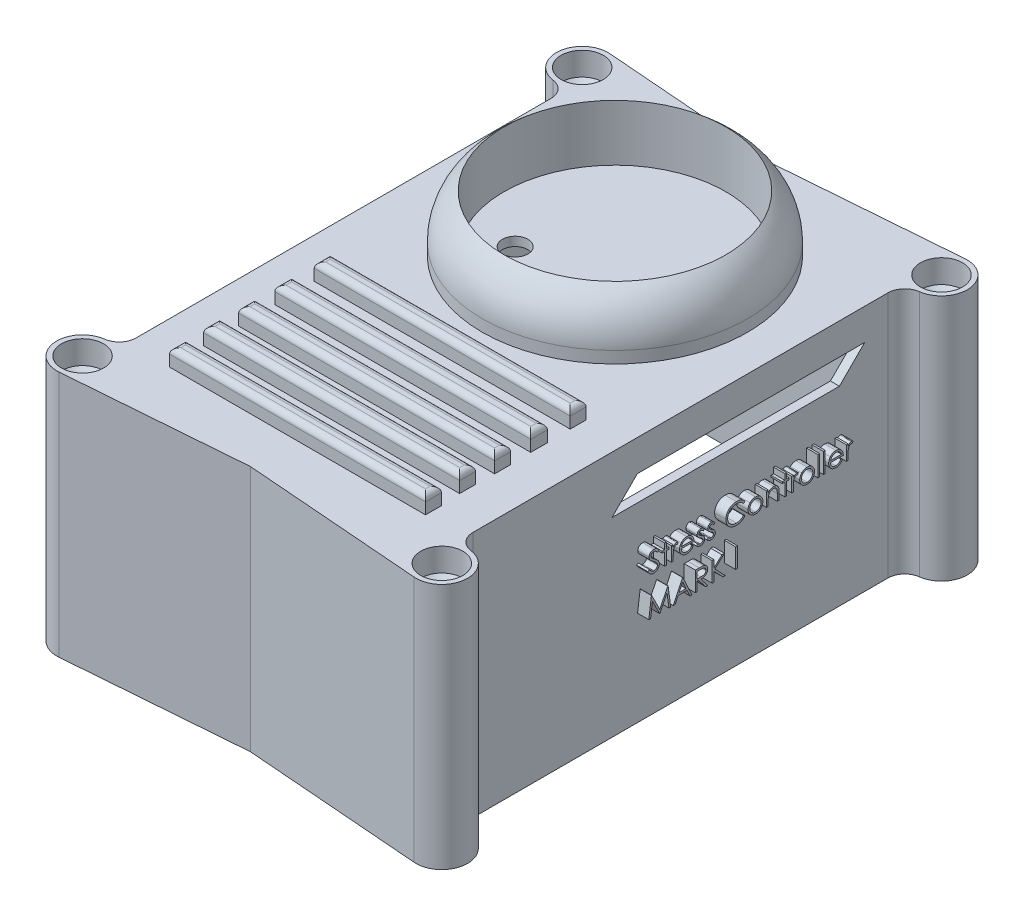
SolidWorks part; units mm, degrees
material "PP Copolymer"
ref_plane "Front Plane" through (0, 0, 0) normal (0, 0, 1) x (1, 0, 0)
ref_plane "Top Plane" through (0, 0, 0) normal (0, 1, 0) x (1, 0, 0)
ref_plane "Right Plane" through (0, 0, 0) normal (1, 0, 0) x (0, 0, -1)
sketch "Sketch1" plane through (0, 0, 0) normal (0, 1, 0) x (1, 0, 0)
  line L1 (-30, 44.5) -> (30, 44.5)
  line L2 (-30, 44.5) -> (-30, -44.5)
  line L3 (-30, -44.5) -> (30, -44.5)
  line L4 (30, 44.5) -> (30, -44.5)
  line L5 (-30, 44.5) -> (30, -44.5) construction
  line L6 (-30, -44.5) -> (30, 44.5) construction
  point P0 (0, 0)
  dimension "D1" = 60
  dimension "D2" = 89
extrude "BASE" add sketch "Sketch1" along normal blind 9 and the other way blind 35
fillet "OUTSIDE OF BASE" radius 3 4 edges at (-30, -13, -44.5) (30, -13, -44.5) (30, -13, 44.5) (-30, -13, 44.5)
shell "INSIDE OF BASE" thickness 1.6 removed face at (0, -35, 0)
sketch "RPI 3 B + BASE PROFILE" plane through (0, 7.4, 0) normal (0, -1, 0) x (-1, 0, 0)
  line L1 (28, -42.5) -> (-28, -42.5)
  line L2 (28, -42.5) -> (28, 42.5)
  line L3 (28, 42.5) -> (-28, 42.5)
  line L4 (-28, -42.5) -> (-28, 42.5)
  line L5 (28, -42.5) -> (-28, 42.5) construction
  line L6 (28, 42.5) -> (-28, -42.5) construction
  point P0 (0, 0)
  dimension "D1" = 56
  dimension "D2" = 85
ref_plane "ETHERNET PORT REFERENCE PLANE" through (0, 0, 42.5) normal (0, 0, 1) x (1, 0, 0)
sketch "FASTENER POINTS" plane through (0, 7.4, 0) normal (0, -1, 0) x (-1, 0, 0)
  line L0 (28, 42.5) -> (-28, 42.5) construction
  line L1 (-24.5, 39) -> (24.5, 39) construction
  line L2 (-24.5, 39) -> (-24.5, -19) construction
  line L3 (-24.5, -19) -> (24.5, -19) construction
  line L4 (24.5, 39) -> (24.5, -19) construction
  line L5 (0, 39) -> (0, 42.5) construction
  point P0 (-24.5, 39)
  point P6 (-24.5, -19)
  point P7 (24.5, 39)
  point P8 (24.5, -19)
  dimension "D1" = 49
  dimension "D2" = 58
  dimension "D3" = 3.5
sketch "Sketch22" plane through (0, -35, 0) normal (0, -1, 0) x (1, 0, 0)
  line L3 (-31.6414, 49.086) -> (27, 44.5)
  line L8 (-27, 44.5) -> (27, 44.5)
  line L10 (-30, 41.5) -> (-30, 39.7295)
  line L11 (-30, -41.5) -> (-30, 41.5) construction
  line L12 (-30, 39.7295) -> (-32.3586, 39.914)
  line L14 (-27, 44.5) -> (27, 44.5) construction
  arc A1 (-27, 44.5) -> (-30, 41.5) centre (-27, 41.5) ccw construction
  arc A2 (-27, 44.5) -> (-30, 41.5) centre (-27, 41.5) ccw
  arc A3 (-32.3586, 39.914) -> (-31.6414, 49.086) centre (-32, 44.5) cw
  dimension "D1" = 4.6
  dimension "D3" = 2
extrude "TOP FASTENING BODY" add sketch "Sketch22" against normal up to surface (44 mm away) up to face at (0, 9, 0)
hole_wizard "CBORE for M4 SHCS1" positions "Sketch23" profile "Sketch24" counterbore size "M4" standard "ANSI Metric" end condition through all
sketch "Sketch23" plane through (0, 9, 0) normal (0, 1, 0) x (1, 0, 0)
  arc A1 (-32.3586, -39.914) -> (-31.6414, -49.086) centre (-32, -44.5) ccw construction
  point P0 (-32, -44.5)
sketch "Sketch24" plane through (-32, 9, 44.5) normal (1, 0, 0) x (0, 0, 1)
  line L0 (0, 0) -> (0, 44)
  line L1 (0, 44) -> (2.4, 44)
  line L3 (2.4, 44) -> (2.4, 4)
  line L4 (2.4, 4) -> (3.75, 4)
  line L5 (3.75, 4) -> (3.75, 0)
  line L7 (3.75, 0) -> (0, 0)
  line L11 (0, -6.35) -> (0, 107.95) construction
  dimension "Thru Hole Dia." = 4.8
  dimension "Thru Hole Depth" = 44
  dimension "C'Bore Dia." = 7.5
  dimension "C'Bore Depth" = 4
mirror "TFB M H" about plane through (0, 0, 0) normal (1, 0, 0) of "CBORE for M4 SHCS1", "TOP FASTENING BODY"
mirror "TFB M V" about plane through (0, 0, 0) normal (0, 0, 1) of "TFB M H", "CBORE for M4 SHCS1", "TOP FASTENING BODY"
sketch "Sketch12" plane through (-30, 0, 0) normal (-1, 0, 0) x (0, 0, 1)
  line L1 (-36.1, -31.5) -> (-27.7, -31.5)
  line L2 (-36.1, -31.5) -> (-36.1, -35)
  line L3 (-36.1, -35) -> (-27.7, -35)
  line L4 (-27.7, -31.5) -> (-27.7, -35)
  line L5 (-36.1, -31.5) -> (-27.7, -35) construction
  line L6 (-36.1, -35) -> (-27.7, -31.5) construction
  line L7 (-41.5, -35) -> (41.5, -35) construction
  point P0 (-31.9, -33.25)
  dimension "D1" = 8.4
  dimension "D2" = 3.5
  dimension "D3" = 10.6
extrude "MICROUSB" cut sketch "Sketch12" against normal up to surface (1.6 mm away) up to face at (-28.4, -13.8, 0)
chamfer "3D PRINTING FOR FASTENING FEATURE " distance 1.5 angle 45 4 edges at (32, 5, 46.9) (32, 5, -42.1) (-32, 5, -42.1) (-32, 5, 46.9)
fillet "TFB OUTER" radius 3 4 edges at (30, -13, 39.7295) (30, -13, -39.7295) (-30, -13, -39.7295) (-30, -13, 39.7295)
sketch "Sketch27" plane through (0, -35, 0) normal (0, -1, 0) x (1, 0, 0)
sketch "Sketch28" plane through (30, 0, 0) normal (1, 0, 0) x (0, 0, -1)
  line L1 (33.3779, 0) -> (-21.6221, 0)
  line L2 (33.3779, 0) -> (33.3779, -10)
  line L3 (33.3779, -10) -> (-21.6221, -10)
  line L4 (-21.6221, 0) -> (-21.6221, -10)
  dimension "D1" = 55
  dimension "D2" = 10
sketch "Sketch30" plane through (0, -35, 0) normal (0, -1, 0) x (1, 0, 0)
sketch "Sketch31" plane through (0, 9, 0) normal (0, 1, 0) x (1, 0, 0)
  circle A0 centre (-0.0398, 18.3792) radius 19.75
  circle A1 centre (-0.0398, 18.3792) radius 23.6341
  dimension "D1" = 39.5
extrude "Boss-Extrude1" add sketch "Sketch31" along normal blind 10
fillet "Fillet1" radius 10 1 edges at (-0.0398, 19, 5.255)
sketch "Sketch32" plane through (0, 9, 0) normal (0, 1, 0) x (1, 0, 0)
  circle A0 centre (-10.3263, 10.8907) radius 2.2726
  point P2 (0, 0)
extrude "Cut-Extrude2" cut sketch "Sketch32" against normal blind 10 contours A0
sketch "Sketch33" plane through (30, 0, 0) normal (1, 0, 0) x (0, 0, -1)
  line L0 (-3.2927, 3.4146) -> (32.8172, 3.4146)
  line L1 (32.8172, 3.4146) -> (28.3172, -1.0854)
  line L2 (28.3172, -1.0854) -> (-12.183, -1.0854)
  line L3 (-12.183, -1.0854) -> (-7.683, 3.4146)
  line L4 (-7.683, 3.4146) -> (-4.061, 3.4146)
  line L5 (-4.061, 3.4146) -> (-3.2927, 3.4146)
extrude "Cut-Extrude4" cut sketch "Sketch33" against normal blind 10
sketch "Sketch35" plane through (30, 0, 0) normal (1, 0, 0) x (0, 0, -1)
  text T0 "Stress Controller \r\nMARK I"
extrude "Boss-Extrude2" add sketch "Sketch35" along normal blind 2
sketch "Sketch37" plane through (-30, 0, 0) normal (-1, 0, 0) x (0, 0, 1)
  line L1 (-26.8125, 3.6971) -> (-26.4169, 3.6781)
  line L3 (-26.4169, -4.529) -> (-26.8125, -4.548)
  line L6 (-22.6899, -0.4255) -> (-22.7045, -0.771)
  line L8 (-30.9205, -0.771) -> (-30.935, -0.4255)
  circle A0 centre (-26.8125, -0.4255) radius 4.1225
  circle A1 centre (-26.8125, -0.4255) radius 5.2143
  circle A3 centre (-4.857, -0.4255) radius 5.2143
  circle A4 centre (-4.857, -0.4255) radius 4.1225
  circle A9 centre (17.103, -0.4255) radius 5.2143
  circle A10 centre (17.103, -0.4255) radius 4.1225
extrude "Boss-Extrude5" add sketch "Sketch37" along normal blind 2 contours A1 A0 | A3 A4 | A9 A10 region at (-30, -0.4255, -31.8793) region at (-30, -0.4255, -9.9238) region at (-30, -0.4255, 12.0362)
fillet "Fillet3" radius 1 3 edges at (-32, -0.4255, 22.3174) (-32, -0.4255, 0.3574) (-32, -0.4255, -21.5982)
sketch "Sketch40" plane through (-30, 0, 0) normal (-1, 0, 0) x (0, 0, 1)
  circle A0 centre (-26.8125, -0.4255) radius 4.1225
extrude "Cut-Extrude6" cut sketch "Sketch40" against normal blind 2
sketch "Sketch41" plane through (-30, 0, 0) normal (-1, 0, 0) x (0, 0, 1)
  circle A0 centre (-4.857, -0.4255) radius 4.2143
extrude "Cut-Extrude7" cut sketch "Sketch41" against normal blind 2
sketch "Sketch42" plane through (-30, 0, 0) normal (-1, 0, 0) x (0, 0, 1)
  circle A0 centre (17.103, -0.4255) radius 4.1225
extrude "Cut-Extrude9" cut sketch "Sketch42" against normal blind 2
sketch "Sketch45" plane through (0, 9, 0) normal (0, 1, 0) x (1, 0, 0)
  line L0 (-22.7971, -16.4764) -> (22.7971, -16.4764)
  line L1 (-22.8681, -9.5165) -> (22.7261, -9.5165)
  line L2 (-22.8681, -9.5165) -> (-22.8681, -12.3573)
  line L3 (-22.8681, -12.3573) -> (22.7261, -12.3573)
  line L4 (22.7261, -9.5165) -> (22.7261, -12.3573)
  line L5 (-22.7971, -16.4764) -> (-22.7971, -19.4592)
  line L6 (-22.7971, -19.4592) -> (22.7971, -19.4592)
  line L7 (22.7971, -16.4764) -> (22.7971, -19.4592)
  line L8 (-22.6959, -23.1522) -> (22.8984, -23.1522)
  line L9 (-22.6959, -23.1522) -> (-22.6959, -25.993)
  line L10 (-22.6959, -25.993) -> (22.8984, -25.993)
  line L11 (22.8984, -23.1522) -> (22.8984, -25.993)
  line L12 (-22.7731, -29.3081) -> (22.8211, -29.3081)
  line L13 (-22.7731, -29.3081) -> (-22.7731, -32.1489)
  line L14 (-22.7731, -32.1489) -> (22.8211, -32.1489)
  line L15 (22.8211, -29.3081) -> (22.8211, -32.1489)
  line L16 (-22.5205, -35.6324) -> (23.0737, -35.6324)
  line L17 (-22.5205, -35.6324) -> (-22.5205, -38.4732)
  line L18 (-22.5205, -38.4732) -> (23.0737, -38.4732)
  line L19 (23.0737, -35.6324) -> (23.0737, -38.4732)
extrude "Boss-Extrude6" add sketch "Sketch45" along normal blind 3 contours L2 L1 L4 L3 | L0 L7 L6 L5 | L8 L11 L10 L9 | L12 L15 L14 L13 | L16 L19 L18 L17
fillet "Fillet4" radius 1 20 edges at (23.0737, 12, 37.0528) (0.2766, 12, 38.4732) (0.2766, 12, 35.6324) (-22.5205, 12, 37.0528) (-22.7731, 12, 30.7285) (22.8211, 12, 30.7285) (0.024, 12, 32.1489) (0.024, 12, 29.3081) (22.8984, 12, 24.5726) (-22.6959, 12, 24.5726) (0.1013, 12, 25.993) (0.1013, 12, 23.1522) (0, 12, 16.4764) (-22.7971, 12, 17.9678) (0, 12, 19.4592) (22.7971, 12, 17.9678) (22.7261, 12, 10.9369) (-22.8681, 12, 10.9369) (-0.071, 12, 9.5165) (-0.071, 12, 12.3573)
